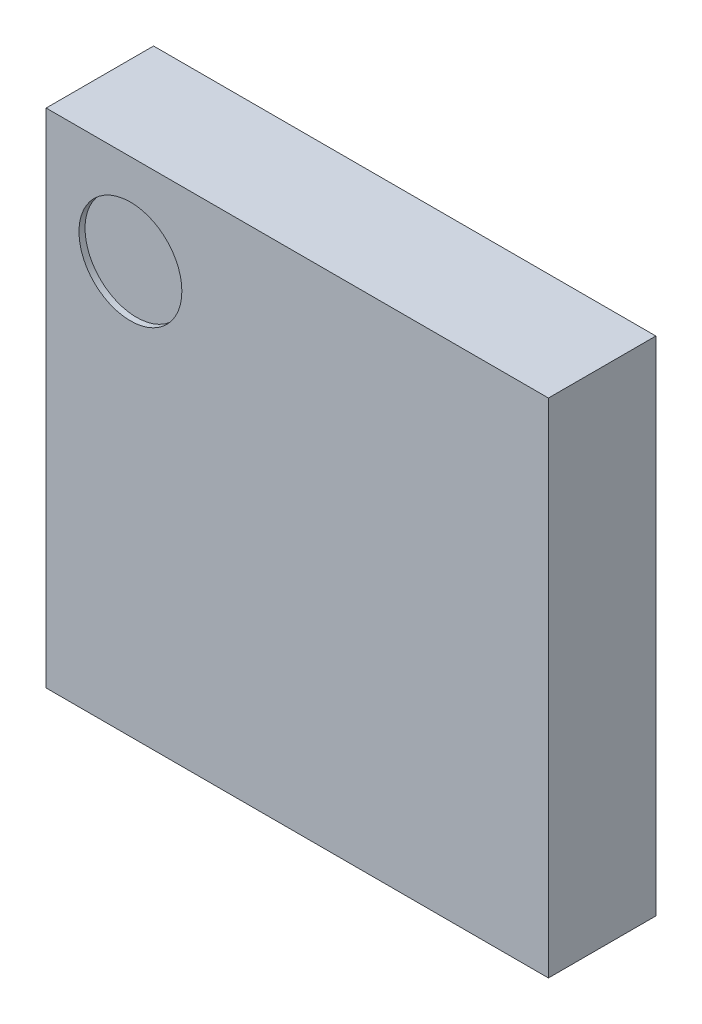
SolidWorks part; units mm, degrees
ref_plane "Front Plane" through (0, 0, 0) normal (0, 0, 1) x (1, 0, 0)
ref_plane "Top Plane" through (0, 0, 0) normal (0, 1, 0) x (1, 0, 0)
ref_plane "Right Plane" through (0, 0, 0) normal (1, 0, 0) x (0, 0, -1)
sketch "Sketch1" plane through (0, 0, 0) normal (0, 0, 1) x (1, 0, 0)
  line L1 (-0.83, -0.83) -> (0.83, -0.83)
  line L2 (-0.83, -0.83) -> (-0.83, 0.83)
  line L3 (-0.83, 0.83) -> (0.83, 0.83)
  line L4 (0.83, -0.83) -> (0.83, 0.83)
  line L5 (-0.83, -0.83) -> (0.83, 0.83) construction
  line L6 (-0.83, 0.83) -> (0.83, -0.83) construction
  point P0 (0, 0)
  dimension "D1" = 1.66
  dimension "D2" = 1.66
extrude "Boss-Extrude1" add sketch "Sketch1" along normal blind 0.355
sketch "Sketch2" plane through (0, 0, 0) normal (0, 1, 0) x (1, 0, 0)
  line L0 (0, 0) -> (0, 0.5655) construction
  line L1 (0.83, 0) -> (-0.83, 0) construction
  line L2 (0.1114, 0) -> (-0.1114, 0)
  arc A0 (0.1114, 0) -> (-0.1114, 0) centre (0, 0.069) ccw
  point P5 (0, 0.2)
  dimension "D1" = 0.262
  dimension "D2" = 0.2
revolve "Revolve1" add sketch "Sketch2" angle 360 about L0 region at (0.0583, 0, -0.0898)
pattern_linear "LPattern1" count 2 spacing 0.5 along (0, 1, 0) count 2 spacing 0.5 along (0, -1, 0) of "Revolve1" pattern seed only yes
pattern_linear "LPattern2" count 2 spacing 0.5 along (1, 0, 0) of "LPattern1"
pattern_linear "LPattern3" count 2 spacing 0.5 along (-1, 0, 0) of "LPattern1"
sketch "Sketch3" plane through (0, 0, 0.355) normal (0, 0, 1) x (1, 0, 0)
  circle A0 centre (-0.5515, 0.5301) radius 0.17
extrude "Cut-Extrude1" cut sketch "Sketch3" against normal blind 0.02
